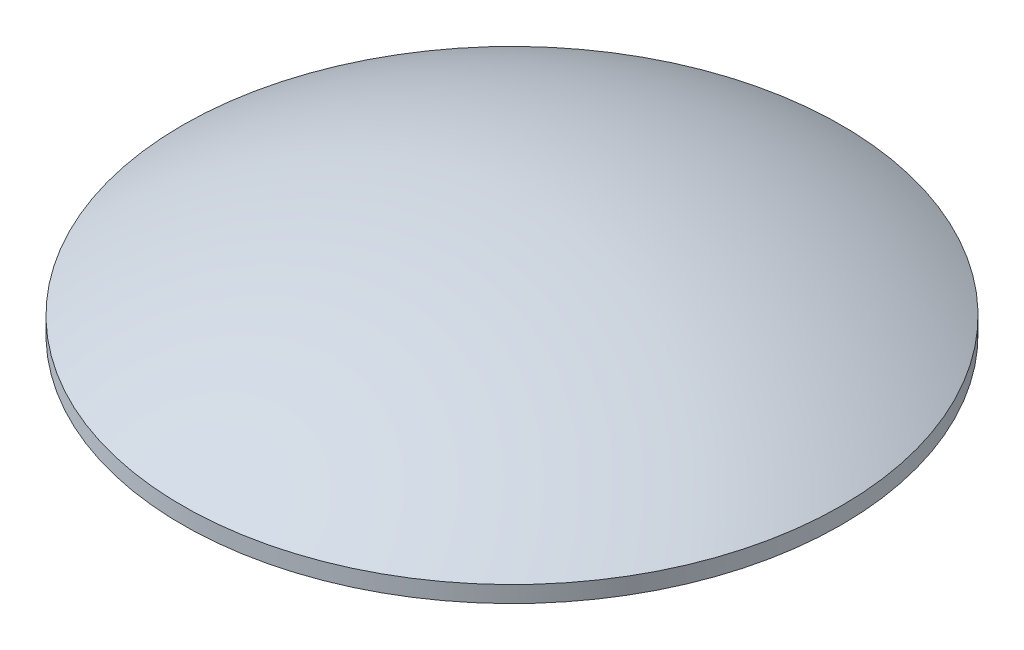
SolidWorks part; units mm, degrees
material "Стекло"
ref_plane "Спереди" through (0, 0, 0) normal (0, 0, 1) x (1, 0, 0)
ref_plane "Сверху" through (0, 0, 0) normal (0, 1, 0) x (1, 0, 0)
ref_plane "Справа" through (0, 0, 0) normal (1, 0, 0) x (0, 0, -1)
sketch "Эскиз1" plane through (0, 0, 0) normal (0, 0, 1) x (1, 0, 0)
  line L0 (0, 0) -> (30, 0)
  line L1 (0, 0) -> (0, 10)
  line L2 (30, 0) -> (30, 1.5)
  circle A2 centre (0, -47.1912) radius 57.1912
  dimension "D1" = 10
  dimension "D2" = 30
  dimension "D3" = 1.5
revolve "Повернуть1" add sketch "Эскиз1" angle 360 about L1 region at (12.1208, 4.0601, 0)
